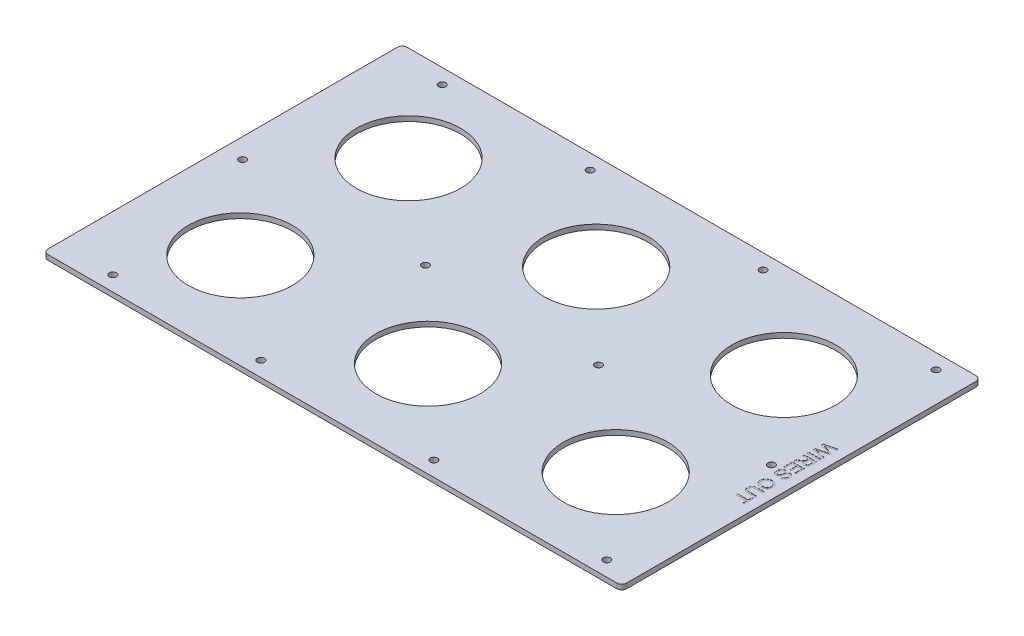
SolidWorks part; units mm, degrees
material "ABS"
ref_plane "Front" through (0, 0, 0) normal (0, 0, 1) x (1, 0, 0)
ref_plane "Top" through (0, 0, 0) normal (0, 1, 0) x (1, 0, 0)
ref_plane "Right" through (0, 0, 0) normal (1, 0, 0) x (0, 0, -1)
sketch "Sketch1" plane through (0, 0, 0) normal (0, 1, 0) x (1, 0, 0)
  line L1 (-180.975, 114.3) -> (180.975, 114.3)
  line L2 (-184.15, 111.125) -> (-184.15, -111.125)
  line L3 (-180.975, -114.3) -> (180.975, -114.3)
  line L4 (184.15, 111.125) -> (184.15, -111.125)
  line L5 (-184.15, 114.3) -> (184.15, -114.3) construction
  line L6 (-184.15, -114.3) -> (184.15, 114.3) construction
  circle A0 centre (119.5086, -53.5178) radius 33.147
  arc A1 (-184.15, -111.125) -> (-180.975, -114.3) centre (-180.975, -111.125) ccw
  arc A2 (180.975, -114.3) -> (184.15, -111.125) centre (180.975, -111.125) ccw
  arc A3 (184.15, 111.125) -> (180.975, 114.3) centre (180.975, 111.125) ccw
  arc A4 (-180.975, 114.3) -> (-184.15, 111.125) centre (-180.975, 111.125) ccw
  circle A5 centre (165.1, 0) radius 2.2479 construction
  circle A6 centre (165.1, 0) radius 2.2479
  circle A7 centre (-171.45, 0) radius 2.2479 construction
  circle A8 centre (-171.45, 0) radius 2.2479
  circle A21 centre (-55.0333, 0) radius 2.2479 construction
  circle A22 centre (55.0333, 0) radius 2.2479 construction
  circle A23 centre (-55.0333, 0) radius 2.2479
  circle A24 centre (55.0333, 0) radius 2.2479
  circle A25 centre (119.5086, 53.5178) radius 33.147
  circle A26 centre (0.0643, 53.5178) radius 33.147
  circle A27 centre (0.0643, -53.5178) radius 33.147
  circle A28 centre (-119.38, 53.5178) radius 33.147
  circle A29 centre (-119.38, -53.5178) radius 33.147
  arc A34 (-143.7521, 103.8733) -> (-143.7521, 3.1623) centre (-119.38, 53.5178) ccw construction
  arc A35 (-24.3078, 103.8733) -> (-24.3078, 3.1623) centre (0.0643, 53.5178) ccw construction
  arc A36 (95.1365, 103.8733) -> (95.1365, 3.1623) centre (119.5086, 53.5178) ccw construction
  arc A37 (-143.7521, -3.1623) -> (-143.7521, -103.8733) centre (-119.38, -53.5178) ccw construction
  arc A38 (-24.3078, -3.1623) -> (-24.3078, -103.8733) centre (0.0643, -53.5178) ccw construction
  arc A39 (95.1365, -3.1623) -> (95.1365, -103.8733) centre (119.5086, -53.5178) ccw construction
  circle A40 centre (-149.225, -104.775) radius 2.2479 construction
  circle A41 centre (-55.0333, -104.775) radius 2.2479 construction
  circle A42 centre (55.0333, -104.775) radius 2.2479 construction
  circle A43 centre (165.1, -104.775) radius 2.2479 construction
  circle A44 centre (-149.225, 104.775) radius 2.2479 construction
  circle A45 centre (-55.0333, 104.775) radius 2.2479 construction
  circle A46 centre (55.0333, 104.775) radius 2.2479 construction
  circle A47 centre (165.1, 104.775) radius 2.2479 construction
  circle A48 centre (-149.225, -104.775) radius 2.2479
  circle A49 centre (-55.0333, -104.775) radius 2.2479
  circle A50 centre (55.0333, -104.775) radius 2.2479
  circle A51 centre (165.1, -104.775) radius 2.2479
  circle A52 centre (-149.225, 104.775) radius 2.2479
  circle A53 centre (-55.0333, 104.775) radius 2.2479
  circle A54 centre (55.0333, 104.775) radius 2.2479
  circle A55 centre (165.1, 104.775) radius 2.2479
  point P0 (0, 0)
  dimension "D3" = 66.294
  dimension "D4" = 3.175
  dimension "D1" = 368.3
  dimension "D2" = 228.6
extrude "Boss-Extrude1" add sketch "Sketch1" along normal blind 3.175
sketch "Sketch2" plane through (0, 3.175, 0) normal (0, 1, 0) x (1, 0, 0)
  line L0 (170.15, 30) -> (170.15, -30) construction
  line L1 (0, 0) -> (184.15, 0) construction
  line L2 (184.15, -111.125) -> (184.15, 111.125) construction
  text T0 "WIRES OUT" font "Arial" height in points 30
  point P7 (170.15, 0)
  dimension "D1" = 14
  dimension "D2" = 60
extrude "Cut-Extrude1" cut sketch "Sketch2" against normal blind 0.1
sketch "Sketch3" plane through (0, 0, 0) normal (0, 1, 0) x (1, 0, 0)
  line L0 (564.5895, -114.2759) -> (564.5895, 114.3581)
  line L1 (-186.5909, 117.2946) -> (1032.6091, 117.2946)
  line L2 (-186.5909, 117.2946) -> (-186.5909, -492.3054)
  line L3 (-186.5909, -492.3054) -> (1032.6091, -492.3054)
  line L4 (1032.6091, 117.2946) -> (1032.6091, -492.3054)
  line L5 (184.5895, -114.2759) -> (-184.2953, -114.2759)
  line L6 (184.5895, -114.2759) -> (184.5895, 114.3581)
  line L7 (184.5895, 114.3581) -> (-184.2953, 114.3581)
  line L8 (-184.2953, -114.2759) -> (-184.2953, 114.3581)
  line L9 (564.5895, -114.2759) -> (195.7047, -114.2759)
  line L10 (195.7047, -114.2759) -> (195.7047, 114.3581)
  line L11 (564.5895, 114.3581) -> (195.7047, 114.3581)
  line L12 (944.5895, -114.2759) -> (944.5895, 114.3581)
  line L13 (944.5895, -114.2759) -> (575.7047, -114.2759)
  line L14 (575.7047, -114.2759) -> (575.7047, 114.3581)
  line L15 (944.5895, 114.3581) -> (575.7047, 114.3581)
  line L16 (564.5895, -364.2759) -> (564.5895, -135.6419)
  line L17 (564.5895, -364.2759) -> (195.7047, -364.2759)
  line L18 (195.7047, -364.2759) -> (195.7047, -135.6419)
  line L19 (564.5895, -135.6419) -> (195.7047, -135.6419)
  line L20 (944.5895, -364.2759) -> (944.5895, -135.6419)
  line L21 (944.5895, -364.2759) -> (575.7047, -364.2759)
  line L22 (575.7047, -364.2759) -> (575.7047, -135.6419)
  line L23 (944.5895, -135.6419) -> (575.7047, -135.6419)
  line L24 (184.5895, -364.2759) -> (184.5895, -135.6419)
  line L25 (184.5895, -364.2759) -> (-184.2953, -364.2759)
  line L26 (-184.2953, -364.2759) -> (-184.2953, -135.6419)
  line L27 (184.5895, -135.6419) -> (-184.2953, -135.6419)
  dimension "D1" = 1219.2
  dimension "D2" = 609.6
  dimension "D3" = 3
  dimension "D4" = 2
